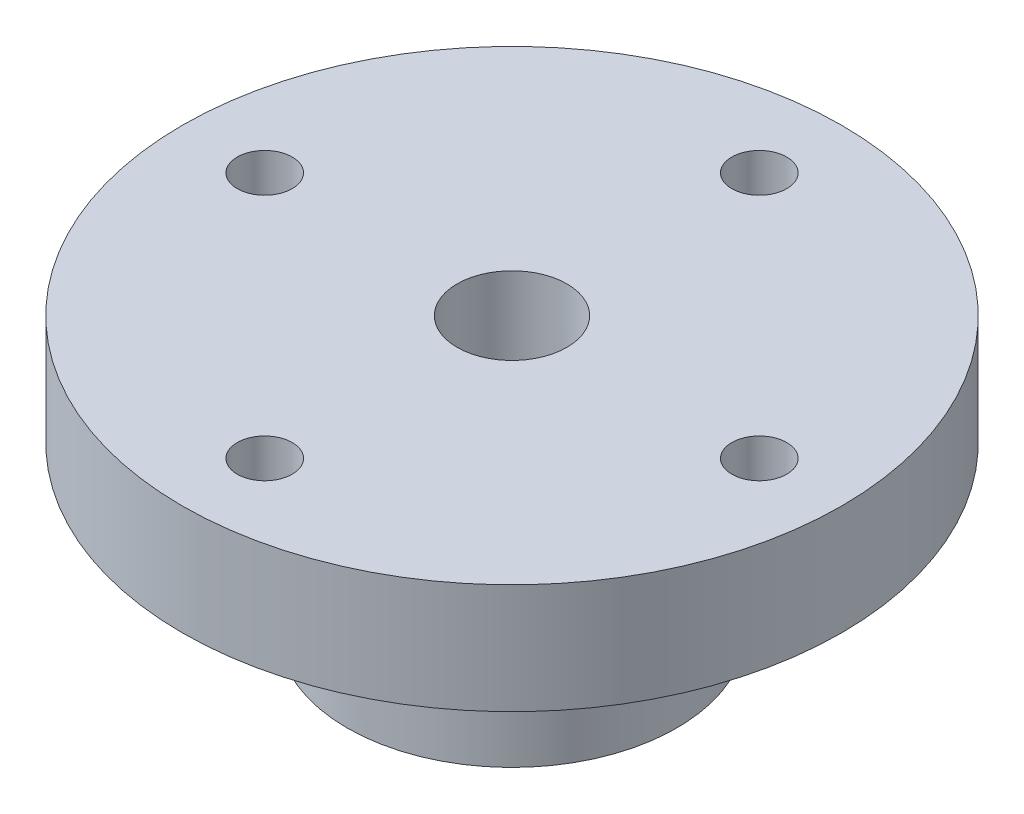
SolidWorks part; units mm, degrees
ref_plane "Front Plane" through (0, 0, 0) normal (0, 0, 1) x (1, 0, 0)
ref_plane "Top Plane" through (0, 0, 0) normal (0, 1, 0) x (1, 0, 0)
ref_plane "Right Plane" through (0, 0, 0) normal (1, 0, 0) x (0, 0, -1)
sketch "Sketch1" plane through (0, 0, 0) normal (0, 1, 0) x (1, 0, 0)
  line L0 (0, 5) -> (0, 11.25) construction
  circle A0 centre (0, 0) radius 5
  circle A1 centre (0, 0) radius 30
  point P16 (0, 0)
extrude "Boss-Extrude4" add sketch "Sketch1" along normal blind 10
sketch "Sketch2" plane through (0, 10, 0) normal (0, 1, 0) x (1, 0, 0)
  line L0 (0, 0) -> (0, 22.5) construction
  circle A0 centre (0, 22.5) radius 2.5
  circle A1 centre (22.5, 0) radius 2.5
  circle A2 centre (0, -22.5) radius 2.5
  circle A3 centre (-22.5, 0) radius 2.5
  point P13 (0, 0)
  dimension "D1" = 4
extrude "Cut-Extrude1" cut sketch "Sketch2" against normal blind 10
sketch "Sketch3" plane through (0, 0, 0) normal (0, -1, 0) x (1, 0, 0)
  circle A0 centre (0, 0) radius 5
  circle A1 centre (0, 0) radius 15
extrude "Boss-Extrude5" add sketch "Sketch3" along normal blind 15
sketch "Sketch4" plane through (0, 0, 0) normal (0, 0, 1) x (1, 0, 0)
  line L0 (0, -15) -> (0, -7.5) construction
  line L1 (-15, -15) -> (15, -15) construction
  circle A0 centre (0, -7.5) radius 2.5
extrude "Cut-Extrude2" cut sketch "Sketch4" along normal blind 54 and the other way blind 39
